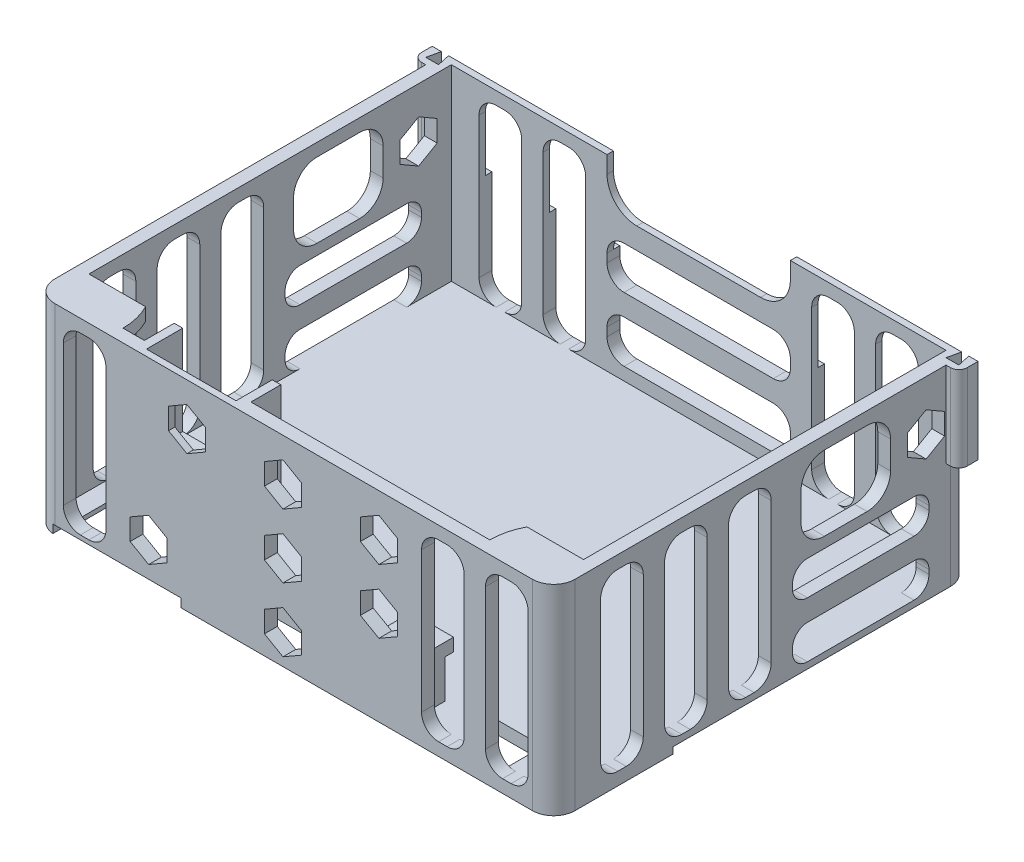
SolidWorks part; units mm, degrees
ref_plane "Front Plane" through (0, 0, 0) normal (0, 0, 1) x (1, 0, 0)
ref_plane "Top Plane" through (0, 0, 0) normal (0, 1, 0) x (1, 0, 0)
ref_plane "Right Plane" through (0, 0, 0) normal (1, 0, 0) x (0, 0, -1)
sketch "Sketch1" plane through (0, 0, 0) normal (0, 1, 0) x (1, 0, 0)
  line L1 (-81.2987, -43.7828) -> (-20.2987, -43.7828)
  line L2 (-81.2987, -43.7828) -> (-81.2987, 5.2172)
  line L3 (-81.2987, 5.2172) -> (-20.2987, 5.2172)
  line L4 (-20.2987, -43.7828) -> (-20.2987, 5.2172)
  dimension "D1" = 61
  dimension "D2" = 49
extrude "Boss-Extrude1" add sketch "Sketch1" along normal blind 23.5
sketch "Sketch2" plane through (0, 23.5, 0) normal (0, 1, 0) x (1, 0, 0)
  line L0 (-81.2987, 5.2172) -> (-81.2987, -43.7828) construction
  line L1 (-79.7987, 3.7172) -> (-21.7987, 3.7172)
  line L2 (-79.7987, 3.7172) -> (-79.7987, -42.2828)
  line L3 (-79.7987, -42.2828) -> (-21.7987, -42.2828)
  line L4 (-21.7987, 3.7172) -> (-21.7987, -42.2828)
  line L5 (-81.2987, -43.7828) -> (-20.2987, -43.7828) construction
  line L6 (-20.2987, -43.7828) -> (-20.2987, 5.2172) construction
  line L7 (-20.2987, 5.2172) -> (-81.2987, 5.2172) construction
  dimension "D1" = 1.5
  dimension "D2" = 1.5
  dimension "D3" = 1.5
  dimension "D4" = 1.5
extrude "Cut-Extrude1" cut sketch "Sketch2" against normal blind 22
sketch "Sketch3" plane through (0, 1.5, 0) normal (0, 1, 0) x (1, 0, 0)
  line L0 (-79.7987, -42.2828) -> (-21.7987, -42.2828) construction
  line L1 (-58.5387, -39.2828) -> (-42.5387, -39.2828)
  line L2 (-58.5387, -39.2828) -> (-58.5387, -42.2828)
  line L3 (-58.5387, -42.2828) -> (-42.5387, -42.2828)
  line L4 (-42.5387, -39.2828) -> (-42.5387, -42.2828)
  line L5 (-21.7987, -42.2828) -> (-21.7987, 3.7172) construction
  line L6 (-32.3987, -38.1328) -> (-27.1987, -38.1328)
  line L7 (-32.3987, -38.1328) -> (-32.3987, -42.2828)
  line L8 (-32.3987, -42.2828) -> (-27.1987, -42.2828)
  line L9 (-27.1987, -38.1328) -> (-27.1987, -42.2828)
  line L10 (-65.5387, -37.2828) -> (-77.5387, -37.2828)
  line L11 (-65.5387, -37.2828) -> (-65.5387, -42.2828)
  line L12 (-65.5387, -42.2828) -> (-77.5387, -42.2828)
  line L13 (-77.5387, -37.2828) -> (-77.5387, -42.2828)
  dimension "D1" = 3
  dimension "D2" = 5.4
  dimension "D3" = 5.2
  dimension "D4" = 10.14
  dimension "D5" = 4.15
  dimension "D6" = 7
  dimension "D7" = 12
  dimension "D8" = 16
  dimension "D9" = 5
extrude "Cut-Extrude2" cut sketch "Sketch3" against normal blind 1.5
sketch "Sketch4" plane through (0, 23.5, 0) normal (0, 1, 0) x (1, 0, 0)
  line L0 (-20.2987, 5.2172) -> (-81.2987, 5.2172) construction
  line L1 (-61.5487, 5.2172) -> (-40.0487, 5.2172)
  line L2 (-61.5487, 5.2172) -> (-61.5487, 3.7172)
  line L3 (-61.5487, 3.7172) -> (-40.0487, 3.7172)
  line L4 (-40.0487, 5.2172) -> (-40.0487, 3.7172)
  line L5 (-21.7987, 3.7172) -> (-79.7987, 3.7172) construction
  dimension "D1" = 18.25
  dimension "D2" = 18.25
extrude "Cut-Extrude3" cut sketch "Sketch4" against normal blind 5.5
sketch "Sketch5" plane through (-81.2987, 0, 0) normal (-1, 0, 0) x (0, 0, 1)
  line L0 (-5.2172, 23.5) -> (43.7828, 23.5) construction
  line L1 (4.2828, 22) -> (14.7828, 22)
  line L2 (4.2828, 22) -> (4.2828, 13.25)
  line L3 (4.2828, 13.25) -> (14.7828, 13.25)
  line L4 (14.7828, 22) -> (14.7828, 13.25)
  dimension "D1" = 10.5
  dimension "D2" = 8.75
  dimension "D3" = 1.5
  dimension "D4" = 8
extrude "Cut-Extrude6" cut sketch "Sketch5" against normal blind 61
sketch "Sketch8" plane through (0, 1.5, 0) normal (0, 1, 0) x (1, 0, 0)
  line L0 (-42.5387, -42.2828) -> (-32.3987, -42.2828) construction
  line L1 (-37.5387, -42.2828) -> (-42.5387, -42.2828)
  line L2 (-37.5387, -42.2828) -> (-37.5387, -39.2828)
  line L3 (-37.5387, -39.2828) -> (-42.5387, -39.2828)
  line L4 (-42.5387, -42.2828) -> (-42.5387, -39.2828)
  line L6 (-58.5387, -42.2828) -> (-63.5387, -42.2828)
  line L7 (-58.5387, -42.2828) -> (-58.5387, -39.2828)
  line L8 (-58.5387, -39.2828) -> (-63.5387, -39.2828)
  line L9 (-63.5387, -42.2828) -> (-63.5387, -39.2828)
  dimension "D1" = 5
  dimension "D2" = 5
extrude "Boss-Extrude2" add sketch "Sketch8" along normal blind 6
sketch "Sketch9" plane through (0, 0, 39.2828) normal (0, 0, -1) x (-1, 0, 0)
  line L0 (37.5387, 7.5) -> (42.5387, 7.5) construction
  line L1 (37.5387, 7.5) -> (42.5387, 7.5)
  line L2 (37.5387, 7.5) -> (37.5387, 6)
  line L3 (37.5387, 6) -> (42.5387, 6)
  line L4 (42.5387, 7.5) -> (42.5387, 6)
  line L5 (42.5387, 7.5) -> (42.5387, 1.5) construction
  line L6 (58.5387, 7.5) -> (63.5387, 7.5) construction
  line L7 (58.5387, 7.5) -> (63.5387, 7.5)
  line L8 (58.5387, 7.5) -> (58.5387, 6)
  line L9 (58.5387, 6) -> (63.5387, 6)
  line L10 (63.5387, 7.5) -> (63.5387, 6)
  line L11 (63.5387, 7.5) -> (63.5387, 1.5) construction
  dimension "D1" = 1.5
  dimension "D2" = 1.5
extrude "Boss-Extrude3" add sketch "Sketch9" along normal blind 1
sketch "Sketch10" plane through (0, 0, 42.2828) normal (0, 0, -1) x (-1, 0, 0)
  line L0 (79.7987, 23.5) -> (21.7987, 23.5) construction
  line L1 (58.2987, 23.5) -> (68.7987, 23.5)
  line L2 (58.2987, 23.5) -> (58.2987, 13)
  line L3 (58.2987, 13) -> (68.7987, 13)
  line L4 (68.7987, 23.5) -> (68.7987, 13)
  line L5 (79.7987, 1.5) -> (79.7987, 23.5) construction
  dimension "D1" = 10.5
  dimension "D2" = 10.5
  dimension "D3" = 0
  dimension "D4" = 11
extrude "Cut-Extrude8" cut sketch "Sketch10" against normal blind 0.75
sketch "Sketch11" plane through (0, 0, 42.2828) normal (0, 0, -1) x (-1, 0, 0)
  line L1 (58.2987, 23.5) -> (57.2987, 23.5)
  line L2 (58.2987, 23.5) -> (58.2987, 12)
  line L3 (58.2987, 12) -> (57.2987, 12)
  line L4 (57.2987, 23.5) -> (57.2987, 12)
  line L5 (68.7987, 13) -> (58.2987, 13)
  line L6 (68.7987, 13) -> (68.7987, 12)
  line L7 (68.7987, 12) -> (58.2987, 12)
  line L8 (58.2987, 13) -> (58.2987, 12)
  line L9 (68.7987, 23.5) -> (69.7987, 23.5)
  line L10 (68.7987, 23.5) -> (68.7987, 12)
  line L11 (68.7987, 12) -> (69.7987, 12)
  line L12 (69.7987, 23.5) -> (69.7987, 12)
  line M8 (68.7987, 13) -> (58.2987, 13)
  line M30 (79.7987, 23.5) -> (68.7987, 23.5)
  line M31 (68.7987, 23.5) -> (68.7987, 13)
  dimension "D1" = 1
  dimension "D2" = 1
  dimension "D3" = 1
  dimension "D4" = 0
extrude "Boss-Extrude4" add sketch "Sketch11" along normal blind 3.5 contours L7 L6 L2 M8 | L12 L6 L11 M30 M31
sketch "Sketch12" plane through (0, 23.5, 0) normal (0, 1, 0) x (1, 0, 0)
  line L1 (-21.7987, -42.2828) -> (-29.2987, -42.2828)
  line L2 (-21.7987, -42.2828) -> (-21.7987, -34.7828)
  line L3 (-21.7987, -34.7828) -> (-29.2987, -34.7828)
  line L4 (-29.2987, -42.2828) -> (-29.2987, -34.7828)
  line L5 (-79.7987, -42.2828) -> (-72.2987, -42.2828)
  line L6 (-79.7987, -42.2828) -> (-79.7987, -34.7828)
  line L7 (-79.7987, -34.7828) -> (-72.2987, -34.7828)
  line L8 (-72.2987, -42.2828) -> (-72.2987, -34.7828)
  dimension "D1" = 7.5
  dimension "D2" = 7.5
  dimension "D3" = 7.5
  dimension "D4" = 7.5
extrude "Boss-Extrude5" add sketch "Sketch12" against normal blind 1.5
fillet "Fillet1" radius 2.75 1 edges at (-80.5487, 13.25, 14.7828)
fillet "Fillet2" radius 2.75 1 edges at (-80.5487, 22, 14.7828)
fillet "Fillet3" radius 2.75 1 edges at (-80.5487, 22, 4.2828)
fillet "Fillet4" radius 2.75 1 edges at (-80.5487, 13.25, 4.2828)
fillet "Fillet5" radius 3.5 1 edges at (-40.0487, 18, -4.4672)
fillet "Fillet6" radius 3.5 1 edges at (-61.5487, 18, -4.4672)
fillet "Fillet7" radius 7.5 5 edges at (-29.2987, 22, 38.5328) (-25.5487, 22, 34.7828) (-29.2987, 22.75, 34.7828) (-25.5487, 23.5, 34.7828) (-29.2987, 23.5, 38.5328)
fillet "Fillet8" radius 7.5 5 edges at (-76.0487, 22, 34.7828) (-72.2987, 22, 38.5328) (-72.2987, 22.75, 34.7828) (-72.2987, 23.5, 38.5328) (-76.0487, 23.5, 34.7828)
fillet "Fillet9" radius 2.5 1 edges at (-20.2987, 11.75, -5.2172)
fillet "Fillet10" radius 2.5 1 edges at (-81.2987, 11.75, -5.2172)
fillet "Fillet11" radius 2.5 1 edges at (-81.2987, 11.75, 43.7828)
fillet "Fillet12" radius 2.5 1 edges at (-20.2987, 11.75, 43.7828)
sketch "Sketch13" plane through (-20.2987, 0, 0) normal (1, 0, 0) x (0, 0, -1)
  line L0 (-41.2828, 23.5) -> (2.7172, 23.5) construction
  line L1 (-36.2828, 22) -> (-35.2828, 22)
  line L2 (-38.2828, 20) -> (-38.2828, 3.5)
  line L3 (-36.2828, 1.5) -> (-35.2828, 1.5)
  line L4 (-33.2828, 20) -> (-33.2828, 3.5)
  line L5 (-28.7828, 22) -> (-27.7828, 22)
  line L6 (-30.7828, 20) -> (-30.7828, 3.5)
  line L7 (-28.7828, 1.5) -> (-27.7828, 1.5)
  line L8 (-25.7828, 20) -> (-25.7828, 3.5)
  line L9 (-21.2828, 22) -> (-20.2828, 22)
  line L10 (-23.2828, 20) -> (-23.2828, 3.5)
  line L11 (-21.2828, 1.5) -> (-20.2828, 1.5)
  line L12 (-18.2828, 20) -> (-18.2828, 3.5)
  line L17 (-41.2828, 0) -> (2.7172, 0) construction
  line L18 (-38.2828, 7.5) -> (-38.2828, 6) construction
  arc A0 (-36.2828, 22) -> (-38.2828, 20) centre (-36.2828, 20) ccw
  arc A1 (-35.2828, 22) -> (-33.2828, 20) centre (-35.2828, 20) cw
  arc A2 (-28.7828, 22) -> (-30.7828, 20) centre (-28.7828, 20) ccw
  arc A3 (-27.7828, 22) -> (-25.7828, 20) centre (-27.7828, 20) cw
  arc A4 (-21.2828, 22) -> (-23.2828, 20) centre (-21.2828, 20) ccw
  arc A5 (-20.2828, 22) -> (-18.2828, 20) centre (-20.2828, 20) cw
  arc A6 (-20.2828, 1.5) -> (-18.2828, 3.5) centre (-20.2828, 3.5) ccw
  arc A7 (-23.2828, 3.5) -> (-21.2828, 1.5) centre (-21.2828, 3.5) ccw
  arc A8 (-27.7828, 1.5) -> (-25.7828, 3.5) centre (-27.7828, 3.5) ccw
  arc A9 (-30.7828, 3.5) -> (-28.7828, 1.5) centre (-28.7828, 3.5) ccw
  arc A10 (-35.2828, 1.5) -> (-33.2828, 3.5) centre (-35.2828, 3.5) ccw
  arc A11 (-38.2828, 3.5) -> (-36.2828, 1.5) centre (-36.2828, 3.5) ccw
  point P14 (-38.2828, 22)
  point P23 (-33.2828, 22)
  point P26 (-30.7828, 22)
  point P29 (-25.7828, 22)
  point P32 (-23.2828, 22)
  point P35 (-18.2828, 22)
  dimension "D4" = 2
  dimension "D1" = 5
  dimension "D2" = 5
  dimension "D3" = 5
  dimension "D5" = 2.5
  dimension "D6" = 2.5
  dimension "D8" = 1.5
  dimension "D9" = 1.5
  dimension "D10" = 1.5
  dimension "D12" = 1.5
  dimension "D13" = 1.5
  dimension "D14" = 1.5
  dimension "D16" = 0
extrude "Cut-Extrude10" cut sketch "Sketch13" against normal blind 61
fillet "Fillet13" radius 2.75 1 edges at (-21.0487, 13.25, 14.7828)
fillet "Fillet14" radius 2.75 1 edges at (-21.0487, 22, 14.7828)
fillet "Fillet15" radius 2.75 1 edges at (-21.0487, 13.25, 4.2828)
fillet "Fillet16" radius 2.75 1 edges at (-21.0487, 22, 4.2828)
sketch "Sketch16" plane through (-20.2987, 0, 0) normal (1, 0, 0) x (0, 0, -1)
  line L0 (-4.2828, 19.25) -> (-4.2828, 16) construction
  line L1 (-0.1178, 20.125) -> (-2.2828, 18.875)
  line L2 (-2.2828, 18.875) -> (-2.2828, 16.375)
  line L3 (-2.2828, 16.375) -> (-0.1178, 15.125)
  line L4 (-0.1178, 15.125) -> (2.0473, 16.375)
  line L5 (2.0473, 16.375) -> (2.0473, 18.875)
  line L6 (2.0473, 18.875) -> (-0.1178, 20.125)
  circle A0 centre (-0.1178, 17.625) radius 2.1651 construction
  point P10 (-4.2828, 17.625)
  dimension "D1" = 0
  dimension "D2" = 2.5
  dimension "D3" = 2
extrude "Cut-Extrude11" cut sketch "Sketch16" against normal blind 61
sketch "Sketch19" plane through (0, 0, -5.2172) normal (0, 0, -1) x (-1, 0, 0)
  line L0 (61.5487, 23.5) -> (78.7987, 23.5) construction
  line L1 (66.0487, 22) -> (67.0487, 22)
  line L2 (64.0487, 20) -> (64.0487, 3.5)
  line L3 (66.0487, 1.5) -> (67.0487, 1.5)
  line L4 (69.0487, 20) -> (69.0487, 3.5)
  line L5 (73.5487, 22) -> (74.5487, 22)
  line L6 (71.5487, 20) -> (71.5487, 3.5)
  line L7 (73.5487, 1.5) -> (74.5487, 1.5)
  line L8 (76.5487, 20) -> (76.5487, 3.5)
  line L9 (27.0487, 22) -> (28.0487, 22)
  line L10 (25.0487, 20) -> (25.0487, 3.5)
  line L11 (27.0487, 1.5) -> (28.0487, 1.5)
  line L12 (30.0487, 20) -> (30.0487, 3.5)
  line L13 (34.5487, 22) -> (35.5487, 22)
  line L14 (32.5487, 20) -> (32.5487, 3.5)
  line L15 (34.5487, 1.5) -> (35.5487, 1.5)
  line L16 (37.5487, 20) -> (37.5487, 3.5)
  line L17 (42.0487, 15.5) -> (59.5487, 15.5)
  line L18 (40.0487, 13.5) -> (40.0487, 12.5)
  line L19 (42.0487, 10.5) -> (59.5487, 10.5)
  line L20 (61.5487, 13.5) -> (61.5487, 12.5)
  line L21 (42.0487, 8) -> (59.5487, 8)
  line L22 (40.0487, 6) -> (40.0487, 5)
  line L23 (42.0487, 3) -> (59.5487, 3)
  line L24 (61.5487, 6) -> (61.5487, 5)
  line L25 (22.7987, 0) -> (78.7987, 0) construction
  line L26 (61.5487, 21.5) -> (61.5487, 23.5) construction
  line L27 (40.0487, 21.5) -> (40.0487, 23.5) construction
  line L28 (22.7987, 23.5) -> (40.0487, 23.5) construction
  line L29 (43.5487, 18) -> (58.0487, 18) construction
  arc A0 (25.0487, 3.5) -> (27.0487, 1.5) centre (27.0487, 3.5) ccw
  arc A1 (28.0487, 1.5) -> (30.0487, 3.5) centre (28.0487, 3.5) ccw
  arc A2 (32.5487, 3.5) -> (34.5487, 1.5) centre (34.5487, 3.5) ccw
  arc A3 (35.5487, 1.5) -> (37.5487, 3.5) centre (35.5487, 3.5) ccw
  arc A4 (42.0487, 8) -> (40.0487, 6) centre (42.0487, 6) ccw
  arc A5 (40.0487, 5) -> (42.0487, 3) centre (42.0487, 5) ccw
  arc A6 (59.5487, 8) -> (61.5487, 6) centre (59.5487, 6) cw
  arc A7 (59.5487, 3) -> (61.5487, 5) centre (59.5487, 5) ccw
  arc A8 (64.0487, 3.5) -> (66.0487, 1.5) centre (66.0487, 3.5) ccw
  arc A9 (67.0487, 1.5) -> (69.0487, 3.5) centre (67.0487, 3.5) ccw
  arc A10 (71.5487, 3.5) -> (73.5487, 1.5) centre (73.5487, 3.5) ccw
  arc A11 (74.5487, 1.5) -> (76.5487, 3.5) centre (74.5487, 3.5) ccw
  arc A12 (74.5487, 22) -> (76.5487, 20) centre (74.5487, 20) cw
  arc A13 (73.5487, 22) -> (71.5487, 20) centre (73.5487, 20) ccw
  arc A14 (67.0487, 22) -> (69.0487, 20) centre (67.0487, 20) cw
  arc A15 (66.0487, 22) -> (64.0487, 20) centre (66.0487, 20) ccw
  arc A16 (59.5487, 15.5) -> (61.5487, 13.5) centre (59.5487, 13.5) cw
  arc A17 (59.5487, 10.5) -> (61.5487, 12.5) centre (59.5487, 12.5) ccw
  arc A18 (40.0487, 12.5) -> (42.0487, 10.5) centre (42.0487, 12.5) ccw
  arc A19 (42.0487, 15.5) -> (40.0487, 13.5) centre (42.0487, 13.5) ccw
  arc A20 (35.5487, 22) -> (37.5487, 20) centre (35.5487, 20) cw
  arc A21 (34.5487, 22) -> (32.5487, 20) centre (34.5487, 20) ccw
  arc A22 (28.0487, 22) -> (30.0487, 20) centre (28.0487, 20) cw
  arc A23 (27.0487, 22) -> (25.0487, 20) centre (27.0487, 20) ccw
  point P46 (40.0487, 8)
  point P49 (40.0487, 3)
  point P56 (64.0487, 1.5)
  point P59 (69.0487, 1.5)
  point P62 (71.5487, 1.5)
  point P65 (76.5487, 1.5)
  point P80 (40.0487, 10.5)
  point P83 (40.0487, 15.5)
  point P86 (37.5487, 22)
  point P89 (32.5487, 22)
  point P92 (30.0487, 22)
  point P95 (25.0487, 22)
  dimension "D25" = 2
  dimension "D1" = 1.5
  dimension "D2" = 1.5
  dimension "D3" = 5
  dimension "D4" = 5
  dimension "D5" = 2.5
  dimension "D6" = 1.5
  dimension "D7" = 1.5
  dimension "D8" = 2.5
  dimension "D9" = 2.5
  dimension "D10" = 5
  dimension "D11" = 5
  dimension "D12" = 2.5
  dimension "D13" = 1.5
  dimension "D14" = 1.5
  dimension "D15" = 1.5
  dimension "D16" = 1.5
  dimension "D17" = 2.5
  dimension "D18" = 2.5
  dimension "D19" = 2.5
  dimension "D20" = 2.5
  dimension "D21" = 5
  dimension "D22" = 5
  dimension "D23" = 2.5
  dimension "D24" = 2.5
extrude "Cut-Extrude12" cut sketch "Sketch19" against normal blind 1.5
sketch "Sketch20" plane through (-20.2987, 0, 0) normal (1, 0, 0) x (0, 0, -1)
  line L0 (-41.2828, 0) -> (2.7172, 0) construction
  line L1 (-1.5328, 1.5) -> (-14.0328, 1.5)
  line L2 (0.2172, 3.25) -> (0.2172, 3.75)
  line L3 (-1.5328, 5.5) -> (-14.0328, 5.5)
  line L4 (-15.7828, 3.25) -> (-15.7828, 3.75)
  line L5 (-1.5328, 8) -> (-14.0328, 8)
  line L6 (0.2172, 9.75) -> (0.2172, 10.25)
  line L7 (-1.5328, 12) -> (-14.0328, 12)
  line L8 (-15.7828, 9.75) -> (-15.7828, 10.25)
  line L9 (2.7172, 0) -> (2.7172, 23.5) construction
  line L10 (-18.2828, 3.5) -> (-18.2828, 20) construction
  arc A0 (-14.0328, 12) -> (-15.7828, 10.25) centre (-14.0328, 10.25) ccw
  arc A1 (-14.0328, 8) -> (-15.7828, 9.75) centre (-14.0328, 9.75) cw
  arc A2 (0.2172, 10.25) -> (-1.5328, 12) centre (-1.5328, 10.25) ccw
  arc A3 (-1.5328, 8) -> (0.2172, 9.75) centre (-1.5328, 9.75) ccw
  arc A4 (0.2172, 3.75) -> (-1.5328, 5.5) centre (-1.5328, 3.75) ccw
  arc A5 (-1.5328, 1.5) -> (0.2172, 3.25) centre (-1.5328, 3.25) ccw
  arc A6 (-14.0328, 5.5) -> (-15.7828, 3.75) centre (-14.0328, 3.75) ccw
  arc A7 (-14.0328, 1.5) -> (-15.7828, 3.25) centre (-14.0328, 3.25) cw
  point P16 (-15.7828, 12)
  point P19 (-15.7828, 8)
  point P30 (-15.7828, 5.5)
  point P33 (-15.7828, 1.5)
  dimension "D9" = 1.75
  dimension "D10" = 1.75
  dimension "D1" = 1.5
  dimension "D2" = 2.5
  dimension "D3" = 4
  dimension "D4" = 4
  dimension "D5" = 2.5
  dimension "D6" = 2.5
  dimension "D7" = 2.5
  dimension "D8" = 2.5
extrude "Cut-Extrude14" cut sketch "Sketch20" against normal blind 61
sketch "Sketch21" plane through (0, 0, 43.0328) normal (0, 0, -1) x (-1, 0, 0)
  line L1 (63.2267, 15.2845) -> (65.784, 16.7609)
  line L2 (65.784, 16.7609) -> (65.784, 19.7138)
  line L3 (65.784, 19.7138) -> (63.2267, 21.1902)
  line L4 (63.2267, 21.1902) -> (60.6695, 19.7138)
  line L5 (60.6695, 19.7138) -> (60.6695, 16.7609)
  line L6 (60.6695, 16.7609) -> (63.2267, 15.2845)
  circle A0 centre (63.2267, 18.2373) radius 2.5572 construction
sketch "Sketch22" plane through (0, 0, 42.2828) normal (0, 0, -1) x (-1, 0, 0)
  line L0 (57.2987, 23.5) -> (29.2987, 23.5) construction
  line L1 (75.7987, 22) -> (74.7987, 22)
  line L2 (77.7987, 20) -> (77.7987, 3.5)
  line L3 (75.7987, 1.5) -> (74.7987, 1.5)
  line L4 (72.7987, 20) -> (72.7987, 3.5)
  line L5 (26.2987, 22) -> (25.2987, 22)
  line L6 (28.2987, 20) -> (28.2987, 3.5)
  line L7 (26.2987, 1.5) -> (25.2987, 1.5)
  line L8 (23.2987, 20) -> (23.2987, 3.5)
  line L9 (33.7987, 22) -> (32.7987, 22)
  line L10 (35.7987, 20) -> (35.7987, 3.5)
  line L11 (33.7987, 1.5) -> (32.7987, 1.5)
  line L12 (30.7987, 20) -> (30.7987, 3.5)
  line L13 (78.7987, 23.5) -> (22.7987, 23.5) construction
  line L14 (27.1987, 1.5) -> (21.7987, 1.5) construction
  line L15 (37.5387, 1.5) -> (32.3987, 1.5) construction
  line L16 (21.7987, 1.5) -> (21.7987, 22) construction
  line L17 (79.7987, 1.5) -> (79.7987, 22) construction
  line L18 (79.7987, 1.5) -> (77.5387, 1.5) construction
  arc A0 (32.7987, 1.5) -> (30.7987, 3.5) centre (32.7987, 3.5) cw
  arc A1 (25.2987, 1.5) -> (23.2987, 3.5) centre (25.2987, 3.5) cw
  arc A2 (25.2987, 22) -> (23.2987, 20) centre (25.2987, 20) ccw
  arc A3 (33.7987, 22) -> (35.7987, 20) centre (33.7987, 20) cw
  arc A4 (32.7987, 22) -> (30.7987, 20) centre (32.7987, 20) ccw
  arc A5 (26.2987, 22) -> (28.2987, 20) centre (26.2987, 20) cw
  arc A6 (28.2987, 3.5) -> (26.2987, 1.5) centre (26.2987, 3.5) cw
  arc A7 (35.7987, 3.5) -> (33.7987, 1.5) centre (33.7987, 3.5) cw
  arc A8 (75.7987, 22) -> (77.7987, 20) centre (75.7987, 20) cw
  arc A9 (74.7987, 22) -> (72.7987, 20) centre (74.7987, 20) ccw
  arc A10 (74.7987, 1.5) -> (72.7987, 3.5) centre (74.7987, 3.5) cw
  arc A11 (77.7987, 3.5) -> (75.7987, 1.5) centre (75.7987, 3.5) cw
  point P28 (30.7987, 1.5)
  point P31 (23.2987, 1.5)
  point P42 (28.2987, 1.5)
  point P45 (35.7987, 1.5)
  point P48 (77.7987, 22)
  point P51 (72.7987, 22)
  dimension "D13" = 2
  dimension "D1" = 1.5
  dimension "D2" = 1.5
  dimension "D3" = 0
  dimension "D4" = 0
  dimension "D5" = 5
  dimension "D6" = 5
  dimension "D7" = 1.5
  dimension "D8" = 2.5
  dimension "D9" = 5
  dimension "D10" = 1.5
  dimension "D11" = 2
  dimension "D12" = 0
extrude "Cut-Extrude15" cut sketch "Sketch22" against normal blind 1.5
sketch "Sketch23" plane through (0, 0, 43.0328) normal (0, 0, -1) x (-1, 0, 0)
  line L0 (57.2987, 23.5) -> (29.2987, 23.5) construction
  line L1 (40.7987, 16) -> (42.9638, 17.25)
  line L2 (42.9638, 17.25) -> (42.9638, 19.75)
  line L3 (42.9638, 19.75) -> (40.7987, 21)
  line L4 (40.7987, 21) -> (38.6336, 19.75)
  line L5 (38.6336, 19.75) -> (38.6336, 17.25)
  line L6 (38.6336, 17.25) -> (40.7987, 16)
  line L7 (35.7987, 3.5) -> (35.7987, 20) construction
  line L8 (52.0487, 16) -> (54.2138, 17.25)
  line L9 (54.2138, 17.25) -> (54.2138, 19.75)
  line L10 (54.2138, 19.75) -> (52.0487, 21)
  line L11 (52.0487, 21) -> (49.8836, 19.75)
  line L12 (49.8836, 19.75) -> (49.8836, 17.25)
  line L13 (49.8836, 17.25) -> (52.0487, 16)
  line L14 (63.2987, 16) -> (65.4638, 17.25)
  line L15 (65.4638, 17.25) -> (65.4638, 19.75)
  line L16 (65.4638, 19.75) -> (63.2987, 21)
  line L17 (63.2987, 21) -> (61.1336, 19.75)
  line L18 (61.1336, 19.75) -> (61.1336, 17.25)
  line L19 (61.1336, 17.25) -> (63.2987, 16)
  line L20 (52.0487, 8.5) -> (54.2138, 9.75)
  line L21 (54.2138, 9.75) -> (54.2138, 12.25)
  line L22 (54.2138, 12.25) -> (52.0487, 13.5)
  line L23 (52.0487, 13.5) -> (49.8836, 12.25)
  line L24 (49.8836, 12.25) -> (49.8836, 9.75)
  line L25 (49.8836, 9.75) -> (52.0487, 8.5)
  line L32 (52.0487, 1) -> (54.2138, 2.25)
  line L33 (54.2138, 2.25) -> (54.2138, 4.75)
  line L34 (54.2138, 4.75) -> (52.0487, 6)
  line L35 (52.0487, 6) -> (49.8836, 4.75)
  line L36 (49.8836, 4.75) -> (49.8836, 2.25)
  line L37 (49.8836, 2.25) -> (52.0487, 1)
  line L44 (40.7987, 8.5) -> (42.9638, 9.75)
  line L45 (42.9638, 9.75) -> (42.9638, 12.25)
  line L46 (42.9638, 12.25) -> (40.7987, 13.5)
  line L47 (40.7987, 13.5) -> (38.6336, 12.25)
  line L48 (38.6336, 12.25) -> (38.6336, 9.75)
  line L49 (38.6336, 9.75) -> (40.7987, 8.5)
  line L56 (42.9638, 4.75) -> (40.7987, 6) [skipped]
  line L57 (40.7987, 6) -> (38.6336, 4.75) [skipped]
  line L58 (38.6336, 4.75) -> (38.6336, 2.25) [skipped]
  line L59 (38.6336, 2.25) -> (40.7987, 1) [skipped]
  line L60 (40.7987, 1) -> (42.9638, 2.25) [skipped]
  line L61 (42.9638, 2.25) -> (42.9638, 4.75) [skipped]
  line L62 (63.2987, 13.5) -> (61.1336, 12.25) [skipped]
  line L63 (65.4638, 12.25) -> (63.2987, 13.5) [skipped]
  line L64 (65.4638, 9.75) -> (65.4638, 12.25) [skipped]
  line L65 (63.2987, 8.5) -> (65.4638, 9.75) [skipped]
  line L66 (61.1336, 9.75) -> (63.2987, 8.5) [skipped]
  line L67 (61.1336, 12.25) -> (61.1336, 9.75) [skipped]
  line L68 (65.4638, 4.75) -> (63.2987, 6) [skipped]
  line L69 (63.2987, 6) -> (61.1336, 4.75) [skipped]
  line L70 (61.1336, 4.75) -> (61.1336, 2.25) [skipped]
  line L71 (61.1336, 2.25) -> (63.2987, 1) [skipped]
  line L72 (63.2987, 1) -> (65.4638, 2.25) [skipped]
  line L73 (65.4638, 2.25) -> (65.4638, 4.75) [skipped]
  circle A0 centre (40.7987, 18.5) radius 2.1651 construction
  dimension "D1" = 2.5
  dimension "D2" = 5
  dimension "D3" = 5
  dimension "D4" = 3
  dimension "D5" = 3
extrude "Cut-Extrude18" cut sketch "Sketch23" against normal blind 1.5 and the other way blind 1.5
sketch "Sketch24" plane through (0, 0, 42.2828) normal (0, 0, -1) x (-1, 0, 0)
  line L0 (77.5387, 0) -> (65.5387, 0) construction
  line L1 (67.7987, 7.5) -> (65.6336, 6.25)
  line L2 (65.6336, 6.25) -> (65.6336, 3.75)
  line L3 (65.6336, 3.75) -> (67.7987, 2.5)
  line L4 (67.7987, 2.5) -> (69.9638, 3.75)
  line L5 (69.9638, 3.75) -> (69.9638, 6.25)
  line L6 (69.9638, 6.25) -> (67.7987, 7.5)
  line L7 (72.7987, 20) -> (72.7987, 3.5) construction
  circle A0 centre (67.7987, 5) radius 2.1651 construction
  dimension "D1" = 2.5
  dimension "D2" = 5
  dimension "D3" = 5
extrude "Cut-Extrude19" cut sketch "Sketch24" against normal blind 1.5
sketch "Sketch25" plane through (0, 23.5, 0) normal (0, 1, 0) x (1, 0, 0)
  line L0 (-21.7987, 2.4675) -> (-21.7987, 3.7172)
  line L1 (-20.2987, 2.7172) -> (-22.7987, 2.7172)
  line L2 (-20.2987, 2.7172) -> (-20.2987, 5.2172)
  line L3 (-20.2987, 5.2172) -> (-22.7987, 5.2172)
  line L4 (-22.7987, 2.7172) -> (-22.7987, 5.2172)
  line L5 (-21.7987, -34.7828) -> (-21.7987, 3.7172) construction
  line L6 (-21.7987, 3.7172) -> (-22.9999, 3.7172)
  line L7 (-21.7987, 3.7172) -> (-40.0487, 3.7172) construction
  line L8 (-79.7987, 0.8703) -> (-79.7987, 3.7172)
  line L9 (-81.2987, 2.7172) -> (-78.7987, 2.7172)
  line L10 (-81.2987, 2.7172) -> (-81.2987, 5.2172)
  line L11 (-81.2987, 5.2172) -> (-78.7987, 5.2172)
  line L12 (-78.7987, 2.7172) -> (-78.7987, 5.2172)
  line L13 (-79.7987, 3.7172) -> (-79.7987, -34.7828) construction
  line L14 (-79.7987, 3.7172) -> (-77.9316, 3.7172)
  line L15 (-61.5487, 3.7172) -> (-79.7987, 3.7172) construction
  line L16 (-77.9316, 3.7172) -> (-79.7987, 0.8703)
  arc A0 (-22.9999, 3.7172) -> (-21.7987, 2.4675) centre (-22.9999, 2.515) cw
  arc M4 (-20.2987, 2.7172) -> (-22.7987, 5.2172) centre (-22.7987, 2.7172) ccw
  arc M24 (-78.7987, 5.2172) -> (-81.2987, 2.7172) centre (-78.7987, 2.7172) ccw
extrude "Boss-Extrude6" add sketch "Sketch25" against normal blind 10 contours L2 L3 M4 | L11 L10 M24
sketch "Sketch26" plane through (0, 0, -5.2172) normal (0, 0, -1) x (-1, 0, 0)
  line L0 (20.2987, 23.5) -> (22.7987, 21.5)
  line L1 (20.2987, 23.5) -> (22.7987, 23.5)
  line L2 (20.2987, 23.5) -> (20.2987, 13.5)
  line L3 (20.2987, 13.5) -> (22.7987, 13.5)
  line L4 (22.7987, 23.5) -> (22.7987, 13.5)
  line L5 (20.2987, 13.5) -> (22.7987, 13.5)
  line L6 (20.2987, 13.5) -> (20.2987, 21.5)
  line L7 (20.2987, 21.5) -> (22.7987, 21.5)
  line L8 (22.7987, 13.5) -> (22.7987, 21.5)
  line L9 (20.2987, 13.5) -> (22.7987, 13.5)
  line L10 (20.2987, 13.5) -> (20.2987, 19.5)
  line L11 (20.2987, 19.5) -> (22.7987, 19.5)
  line L12 (22.7987, 13.5) -> (22.7987, 19.5)
  line L13 (20.2987, 13.5) -> (22.7987, 13.5)
  line L14 (20.2987, 13.5) -> (20.2987, 17.5)
  line L15 (20.2987, 17.5) -> (22.7987, 17.5)
  line L16 (22.7987, 13.5) -> (22.7987, 17.5)
  line L17 (20.2987, 13.5) -> (22.7987, 13.5)
  line L18 (20.2987, 13.5) -> (20.2987, 15.5)
  line L19 (20.2987, 15.5) -> (22.7987, 15.5)
  line L20 (22.7987, 13.5) -> (22.7987, 15.5)
  line L21 (20.2987, 19.5) -> (22.7987, 21.5)
  line L22 (20.2987, 19.5) -> (22.7987, 17.5)
  line L23 (20.2987, 15.5) -> (22.7987, 17.5)
  line L24 (20.2987, 15.5) -> (22.7987, 13.5)
  line L25 (22.7987, 13.5) -> (20.2987, 11)
  line L26 (20.2987, 11) -> (20.2987, 13.5)
  line L27 (20.4391, 13.5) -> (22.7987, 13.5)
  line L28 (20.4391, 13.5) -> (20.2987, 13.5)
  dimension "D1" = 8
  dimension "D2" = 6
  dimension "D3" = 4
  dimension "D4" = 2
sketch "Sketch27" plane through (0, 23.5, 0) normal (0, 1, 0) x (1, 0, 0)
  line L1 (-21.7987, 3.7172) -> (-20.2987, 3.7172)
  line L2 (-21.7987, 3.7172) -> (-21.7987, 5.2172)
  line L3 (-21.7987, 5.2172) -> (-20.2987, 5.2172)
  line L4 (-20.2987, 3.7172) -> (-20.2987, 5.2172)
  line L5 (-21.7987, 5.2172) -> (-18.7987, 5.2172)
  line L6 (-21.7987, 5.2172) -> (-21.7987, 2.2172)
  line L7 (-21.7987, 2.2172) -> (-18.7987, 2.2172)
  line L8 (-18.7987, 5.2172) -> (-18.7987, 2.2172)
  line M5 (-20.2987, -41.2828) -> (-20.2987, 5.2172)
  dimension "D1" = 3
  dimension "D2" = 3
extrude "Boss-Extrude7" add sketch "Sketch27" against normal blind 10 contours L8 L5 L7 M5
sketch "Sketch28" plane through (0, 23.5, 0) normal (0, 1, 0) x (1, 0, 0)
  line L0 (-20.0487, 5.2172) -> (-19.5487, 2.9672)
  line L1 (-18.7987, 5.2172) -> (-40.0487, 5.2172) construction
  line L2 (-19.5487, 2.9672) -> (-21.0487, 2.9672)
  line L3 (-21.0487, 2.9672) -> (-20.5487, 5.2172)
  line L4 (-20.5487, 5.2172) -> (-20.0487, 5.2172)
  line L5 (-18.7987, 5.2172) -> (-18.7987, 2.2172) construction
  line L6 (-21.7987, -34.7828) -> (-21.7987, 3.7172) construction
  line L7 (-20.2987, 2.2172) -> (-18.7987, 2.2172) construction
  dimension "D1" = 1.25
  dimension "D2" = 0.75
  dimension "D3" = 1.25
  dimension "D4" = 0.75
  dimension "D5" = 0.75
extrude "Cut-Extrude23" cut sketch "Sketch28" against normal blind 10
sketch "Sketch31" plane through (0, 23.5, 0) normal (0, 1, 0) x (1, 0, 0)
  line L0 (-61.5487, 5.2172) -> (-81.2987, 5.2172) construction
  line L1 (-79.7987, 5.2172) -> (-82.7987, 5.2172)
  line L2 (-79.7987, 5.2172) -> (-79.7987, 2.2172)
  line L3 (-79.7987, 2.2172) -> (-82.7987, 2.2172)
  line L4 (-82.7987, 5.2172) -> (-82.7987, 2.2172)
  line L5 (-79.7987, 3.7172) -> (-79.7987, -34.7828) construction
  dimension "D1" = 3
  dimension "D2" = 3
  dimension "D3" = 0
extrude "Boss-Extrude9" add sketch "Sketch31" against normal blind 10
sketch "Sketch32" plane through (0, 23.5, 0) normal (0, 1, 0) x (1, 0, 0)
  line L0 (-81.0487, 5.2172) -> (-80.5487, 2.9672)
  line L1 (-61.5487, 5.2172) -> (-82.7987, 5.2172) construction
  line L2 (-80.5487, 2.9672) -> (-82.0487, 2.9672)
  line L3 (-82.0487, 2.9672) -> (-81.5487, 5.2172)
  line L4 (-82.7987, 5.2172) -> (-82.7987, 2.2172) construction
  line L5 (-79.7987, 3.7172) -> (-79.7987, -34.7828) construction
  line L6 (-82.7987, 2.2172) -> (-81.2987, 2.2172) construction
  line L7 (-81.0487, 5.2172) -> (-81.5487, 5.2172)
  dimension "D1" = 0.75
  dimension "D2" = 0.75
  dimension "D3" = 1.25
  dimension "D4" = 1.25
  dimension "D5" = 0.75
extrude "Cut-Extrude24" cut sketch "Sketch32" against normal blind 10
sketch "Sketch33" plane through (0, 23.5, 0) normal (0, 1, 0) x (1, 0, 0)
  line L0 (-82.7987, 5.2172) -> (-82.7987, 2.2172) construction
  line L1 (-18.7987, 5.2172) -> (-82.7987, 5.2172)
  line L2 (-18.7987, 5.2172) -> (-18.7987, 4.4672)
  line L3 (-18.7987, 4.4672) -> (-82.7987, 4.4672)
  line L4 (-82.7987, 5.2172) -> (-82.7987, 4.4672)
  dimension "D1" = 0.75
extrude "Cut-Extrude25" cut sketch "Sketch33" against normal blind 10
sketch "Sketch34" plane through (0, 0, 0) normal (0, -1, 0) x (-1, 0, 0)
  line L0 (65.5387, -37.2828) -> (77.5387, -37.2828) construction
  line L1 (64.5387, -43.2828) -> (65.5387, -43.2828)
  line L2 (64.5387, -43.2828) -> (64.5387, -42.2828)
  line L3 (64.5387, -42.2828) -> (65.5387, -42.2828)
  line L4 (65.5387, -43.2828) -> (65.5387, -42.2828)
  line L5 (64.5387, -36.2828) -> (65.5387, -36.2828)
  line L6 (64.5387, -36.2828) -> (64.5387, -37.2828)
  line L7 (64.5387, -37.2828) -> (65.5387, -37.2828)
  line L8 (65.5387, -36.2828) -> (65.5387, -37.2828)
  line L9 (78.5387, -43.2828) -> (77.5387, -43.2828)
  line L10 (78.5387, -43.2828) -> (78.5387, -42.2828)
  line L11 (78.5387, -42.2828) -> (77.5387, -42.2828)
  line L12 (77.5387, -43.2828) -> (77.5387, -42.2828)
  line L13 (78.5387, -36.2828) -> (77.5387, -36.2828)
  line L14 (78.5387, -36.2828) -> (78.5387, -37.2828)
  line L15 (78.5387, -37.2828) -> (77.5387, -37.2828)
  line L16 (77.5387, -36.2828) -> (77.5387, -37.2828)
  line L17 (72.0387, -37.2828) -> (71.0387, -37.2828)
  line L18 (72.0387, -37.2828) -> (72.0387, -36.2828)
  line L19 (72.0387, -36.2828) -> (71.0387, -36.2828)
  line L20 (71.0387, -37.2828) -> (71.0387, -36.2828)
  line L21 (77.5387, -42.2828) -> (65.5387, -42.2828) construction
  line L22 (72.0387, -42.2828) -> (71.0387, -42.2828)
  line L23 (72.0387, -42.2828) -> (72.0387, -43.2828)
  line L24 (72.0387, -43.2828) -> (71.0387, -43.2828)
  line L25 (71.0387, -42.2828) -> (71.0387, -43.2828)
  dimension "D1" = 1
  dimension "D2" = 1
  dimension "D3" = 1
  dimension "D4" = 1
  dimension "D5" = 1
  dimension "D6" = 1
  dimension "D7" = 1
  dimension "D8" = 1
  dimension "D9" = 1
  dimension "D10" = 1
  dimension "D11" = 1
  dimension "D12" = 1
  dimension "D13" = 5.5
  dimension "D14" = 5.5
fillet "Fillet17" radius 1 1 edges at (-82.7987, 18.5, -2.2172)
fillet "Fillet18" radius 1 1 edges at (-18.7987, 18.5, -2.2172)
sketch "Sketch35" plane through (0, 0, 0) normal (0, -1, 0) x (-1, 0, 0)
  line L0 (65.5387, -37.2828) -> (77.5387, -37.2828) construction
  line L1 (64.0287, -35.7728) -> (65.5287, -35.7728)
  line L2 (64.0287, -35.7728) -> (64.0287, -37.2728)
  line L3 (64.0287, -37.2728) -> (65.5287, -37.2728)
  line L4 (65.5287, -35.7728) -> (65.5287, -37.2728)
  line L5 (70.7887, -35.7828) -> (72.2887, -35.7828)
  line L6 (70.7887, -35.7828) -> (70.7887, -37.2828)
  line L7 (70.7887, -37.2828) -> (72.2887, -37.2828)
  line L8 (72.2887, -35.7828) -> (72.2887, -37.2828)
  line L9 (77.5387, -42.2828) -> (65.5387, -42.2828) construction
  line L14 (79.0487, -43.7928) -> (77.5487, -43.7928)
  line L15 (79.0487, -43.7928) -> (79.0487, -42.2928)
  line L16 (79.0487, -42.2928) -> (77.5487, -42.2928)
  line L17 (77.5487, -43.7928) -> (77.5487, -42.2928)
  line L18 (72.2887, -43.7828) -> (70.7887, -43.7828)
  line L19 (72.2887, -43.7828) -> (72.2887, -42.2828)
  line L20 (72.2887, -42.2828) -> (70.7887, -42.2828)
  line L21 (70.7887, -43.7828) -> (70.7887, -42.2828)
  line L23 (64.0287, -43.7928) -> (65.5287, -43.7928)
  line L24 (64.0287, -43.7928) -> (64.0287, -42.2928)
  line L25 (64.0287, -42.2928) -> (65.5287, -42.2928)
  line L26 (65.5287, -43.7928) -> (65.5287, -42.2928)
  line L27 (79.0487, -35.7728) -> (77.5487, -35.7728)
  line L28 (79.0487, -35.7728) -> (79.0487, -37.2728)
  line L29 (79.0487, -37.2728) -> (77.5487, -37.2728)
  line L30 (77.5487, -35.7728) -> (77.5487, -37.2728)
  dimension "D1" = 0.01
  dimension "D2" = 0.01
  dimension "D3" = 1.5
  dimension "D4" = 1.5
  dimension "D5" = 1.5
  dimension "D6" = 1.5
  dimension "D7" = 0.01
  dimension "D8" = 0.01
  dimension "D9" = 1.5
  dimension "D10" = 1.5
  dimension "D11" = 0.01
  dimension "D12" = 0.01
  dimension "D13" = 1.5
  dimension "D14" = 1.5
  dimension "D15" = 1.5
  dimension "D16" = 1.5
  dimension "D17" = 0.01
  dimension "D18" = 0.01
  dimension "D19" = 1.5
  dimension "D20" = 1.5
  dimension "D21" = 5.26
  dimension "D22" = 5.26
extrude "Cut-Extrude27" cut sketch "Sketch35" against normal blind 1
sketch "Sketch37" plane through (-81.2987, 0, 0) normal (-1, 0, 0) x (0, 0, 1)
  line L0 (-2.7172, 0) -> (41.2828, 0) construction
  line L1 (-0.2172, 1) -> (1.7828, 1)
  line L2 (-0.2172, 1) -> (-0.2172, 0)
  line L3 (-0.2172, 0) -> (1.7828, 0)
  line L4 (1.7828, 1) -> (1.7828, 0)
  line L5 (-5.2172, 0) -> (-5.2172, 13.5) construction
  line L6 (27.2828, 1) -> (25.2828, 1)
  line L7 (27.2828, 1) -> (27.2828, 0)
  line L8 (27.2828, 0) -> (25.2828, 0)
  line L9 (25.2828, 1) -> (25.2828, 0)
  dimension "D1" = 25.5
  dimension "D2" = 2
  dimension "D3" = 2
  dimension "D4" = 5
  dimension "D5" = 1
  dimension "D6" = 1
sketch "Sketch38" plane through (0, 23.5, 0) normal (0, 1, 0) x (1, 0, 0)
  line L0 (-81.2987, 2.2172) -> (-81.2987, -41.2828) construction
  line L1 (-79.7987, -38.7828) -> (-21.7987, -38.7828)
  line L2 (-79.7987, -38.7828) -> (-79.7987, -34.7828)
  line L3 (-79.7987, -34.7828) -> (-21.7987, -34.7828)
  line L4 (-21.7987, -38.7828) -> (-21.7987, -34.7828)
  line L5 (-69.7987, -38.7828) -> (-68.7987, -38.7828) construction
  point P10 (-69.2987, -38.7828)
  dimension "D1" = 1.5
  dimension "D2" = 0
extrude "Cut-Extrude29" cut sketch "Sketch38" against normal blind 1.5
sketch "Sketch40" plane through (0, 0, 0) normal (0, -1, 0) x (-1, 0, 0)
  line L0 (77.5487, -43.7828) -> (72.2887, -43.7828) construction
  line L1 (64.0287, -35.7728) -> (79.0487, -35.7728)
  line L2 (64.0287, -35.7728) -> (64.0287, -43.7828)
  line L3 (64.0287, -43.7828) -> (79.0487, -43.7828)
  line L4 (79.0487, -35.7728) -> (79.0487, -43.7828)
  line L5 (79.0487, -43.7703) -> (79.0487, -42.2928) construction
  dimension "D1" = 0
  dimension "D2" = 0
extrude "Cut-Extrude31" cut sketch "Sketch40" against normal blind 1
sketch "Sketch41" plane through (0, 0, 0) normal (0, -1, 0) x (-1, 0, 0)
  line L0 (20.2987, -41.2828) -> (20.2987, 2.7172) construction
  line L1 (22.7987, -32.2828) -> (78.7987, -32.2828)
  line L2 (20.2987, -29.7828) -> (20.2987, 2.7172)
  line L3 (22.7987, 5.2172) -> (78.7987, 5.2172)
  line L4 (81.2987, -29.7828) -> (81.2987, 2.7172)
  line L5 (22.7987, 5.2172) -> (78.7987, 5.2172) construction
  line L7 (22.2987, -30.7828) -> (79.2987, -30.7828)
  line L8 (22.2987, -30.7828) -> (22.2987, 3.7172)
  line L9 (22.2987, 3.7172) -> (79.2987, 3.7172)
  line L10 (79.2987, -30.7828) -> (79.2987, 3.7172)
  arc A0 (78.7987, -32.2828) -> (81.2987, -29.7828) centre (78.7987, -29.7828) ccw
  arc A1 (22.7987, -32.2828) -> (20.2987, -29.7828) centre (22.7987, -29.7828) cw
  arc A2 (20.2987, 2.7172) -> (22.7987, 5.2172) centre (22.7987, 2.7172) cw
  arc A3 (78.7987, 5.2172) -> (81.2987, 2.7172) centre (78.7987, 2.7172) cw
  point P13 (20.2987, -32.2828)
  point P16 (20.2987, 5.2172)
  dimension "D4" = 2.5
  dimension "D1" = 0
  dimension "D2" = 0
  dimension "D3" = 37.5
  dimension "D5" = 1.5
  dimension "D6" = 1.5
  dimension "D7" = 2
  dimension "D8" = 2
extrude "Cut-Extrude32" cut sketch "Sketch41" against normal blind 0.75
